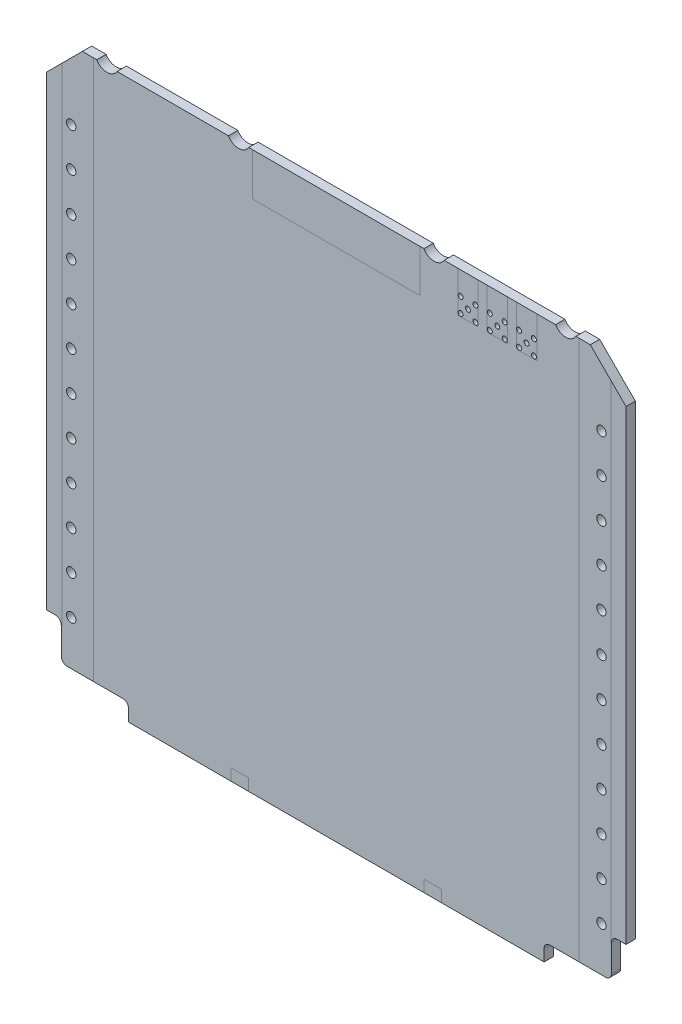
SolidWorks part; units mm, degrees
material "FR4_stuffedProtoboard"
ref_plane "Front Plane" through (0, 0, 0) normal (0, 0, 1) x (1, 0, 0)
ref_plane "Top Plane" through (0, 0, 0) normal (0, 1, 0) x (1, 0, 0)
ref_plane "Right Plane" through (0, 0, 0) normal (1, 0, 0) x (0, 0, -1)
ref_plane "Plane4" through (0, 0, -0.0125) normal (0, 0, -1) x (-1, 0, 0)
sketch "Sketch1" plane through (0, 0, -0.0125) normal (0, 0, -1) x (-1, 0, 0)
  line L4 (49.5, -50) -> (49.5, 45.3)
  line L6 (49.5, 45.3) -> (-49.5, 45.3)
  line L12 (-49.5, 45.3) -> (-49.5, -50)
  line L17 (-49.5, -50) -> (49.5, -50)
  line L18 (0, -50) -> (0, 45.3) construction
  dimension "D7" = 95.3
  dimension "D1" = 99
  dimension "D34" = 50
extrude "basicSize" add sketch "Sketch1" against normal blind 1.6
chamfer "Chamfer1" distance 6.1 angle 45 2 edges at (49.5, 45.3, 0.7875) (-49.5, 45.3, 0.7875)
sketch "Sketch4" plane through (0, 0, 1.5875) normal (0, 0, 1) x (1, 0, 0)
  line L1 (37.4679, 45.3) -> (40.9321, 45.3)
  line L7 (-43.4, 45.3) -> (43.4, 45.3) construction
  line L8 (49.5, 39.2) -> (49.5, -50) construction
  arc A0 (40.9321, 45.3) -> (37.4679, 45.3) centre (39.2, 46.3) cw
  point P5 (39.2, 44.3)
  dimension "D1" = 2
  dimension "D3" = 10.3
  dimension "D2" = 1
extrude "backplaneSideScrewCutout" cut sketch "Sketch4" against normal through all both and the other way through all
pattern_linear "LPattern3" count 2 spacing 22.5 along (-1, 0, 0) of "backplaneSideScrewCutout"
mirror "Mirror3" about plane through (0, 0, 0) normal (1, 0, 0) of "LPattern3"
sketch "Sketch6" plane through (0, 0, 1.5875) normal (0, 0, 1) x (1, 0, 0)
  line L0 (-49.5, -50) -> (-49.5, 39.2) construction
  line L1 (-49.5, -40.4) -> (-47, -40.4)
  line L2 (-49.5, -40.4) -> (-49.5, -50)
  line L4 (-47, -40.4) -> (-47, -47)
  line L5 (49.5, -50) -> (-49.5, -50) construction
  line L6 (-35.5, -50) -> (-49.5, -50)
  line L7 (-35.5, -50) -> (-35.5, -47)
  line L8 (-35.5, -47) -> (-47, -47)
  dimension "D1" = 2.5
  dimension "D2" = 3
  dimension "D3" = 9.6
  dimension "D4" = 14
extrude "Cut-Extrude4" cut sketch "Sketch6" against normal through all
fillet "Fillet1" radius 1 3 edges at (-35.5, -47, 0.7875) (-47, -47, 0.7875) (-47, -40.4, 0.7875)
mirror "Mirror1" about plane through (0, 0, 0) normal (1, 0, 0) of "Cut-Extrude4", "Fillet1"
sketch "Sketch5" plane through (0, 0, 1.5875) normal (0, 0, 1) x (1, 0, 0)
  line L0 (21.23, 41.37) -> (23.77, 38.83) construction
  line L1 (21.23, 38.83) -> (21.23, 41.37) construction
  line L2 (21.23, 41.37) -> (23.77, 41.37) construction
  line L4 (49.5, 39.2) -> (49.5, -40.4) construction
  line L5 (-14.9679, 45.3) -> (14.9679, 45.3) construction
  circle A0 centre (22.5, 40.1) radius 0.425
  circle A1 centre (21.23, 41.37) radius 0.425
  circle A3 centre (21.23, 38.83) radius 0.425
  circle A4 centre (23.77, 41.37) radius 0.425
  circle A5 centre (23.77, 38.83) radius 0.425
  dimension "D2" = 0.85
  dimension "D1" = 2.54
  dimension "D3" = 3.93
  dimension "D4" = 28.27
extrude "Cut-Extrude3" cut sketch "Sketch5" against normal through all
pattern_linear "LPattern2" count 3 spacing 5 along (1, 0, 0) of "Cut-Extrude3"
sketch "partFootprints" plane through (0, 0, 1.5875) normal (0, 0, 1) x (1, 0, 0)
  line L1 (18.4321, 45.3) -> (37.4679, 45.3) construction
  line L6 (20.75, 45.3) -> (20.75, 38.35)
  line L7 (20.75, 38.35) -> (24.25, 38.35)
  line L8 (24.25, 38.35) -> (24.25, 45.3)
  line L9 (24.25, 45.3) -> (20.75, 45.3)
  line L10 (25.75, 45.3) -> (25.75, 38.35)
  line L11 (25.75, 38.35) -> (29.25, 38.35)
  line L12 (29.25, 38.35) -> (29.25, 45.3)
  line L13 (29.25, 45.3) -> (25.75, 45.3)
  line L14 (30.75, 45.3) -> (30.75, 38.35)
  line L15 (30.75, 38.35) -> (34.25, 38.35)
  line L16 (34.25, 38.35) -> (34.25, 45.3)
  line L17 (34.25, 45.3) -> (30.75, 45.3)
  line L19 (32.5, 38.35) -> (32.5, 40.1) construction
  line L23 (22.5, 38.35) -> (22.5, 40.1) construction
  circle A2 centre (22.5, 40.1) radius 0.425 construction
  circle A5 centre (32.5, 40.1) radius 0.425 construction
  dimension "D1" = 1.75
  dimension "D8" = 3.5
  dimension "D6" = 3
extrude "MMCXfootprint" cut sketch "partFootprints" against normal blind 0.0001
sketch "Sketch7" plane through (0, 0, 1.5875) normal (0, 0, 1) x (1, 0, 0)
  line L0 (-14.2875, 45.5) -> (-14.2875, 39.912) construction
  line L1 (-14.2875, 45.3) -> (-14.2875, 38.007)
  line L2 (-12.2428, 38.007) -> (-11.8872, 38.007) construction
  line L3 (-14.2875, 38.007) -> (14.2875, 38.007)
  line L4 (14.2875, 45.5) -> (14.2875, 39.912) construction
  line L5 (14.2875, 45.3) -> (14.2875, 38.007)
  line L7 (-14.9679, 45.3) -> (14.9679, 45.3) construction
  line L8 (-14.2875, 45.3) -> (14.2875, 45.3)
extrude "TigerEyeFootprint" cut sketch "Sketch7" against normal blind 0.0001
sketch "thermalContacts_upper" plane through (0, 0, 1.5875) normal (0, 0, 1) x (1, 0, 0)
  line L0 (-49.5, -40.4) -> (-49.5, 39.2) construction
  line L1 (35.5, -50) -> (-35.5, -50) construction
  line L3 (-46.9, 45.3) -> (-46.9, -41.5)
  line L4 (-37.4679, 45.3) -> (-18.4321, 45.3) construction
  line L23 (-46.9, 45.3) -> (-56.3922, 45.3)
  line L24 (-56.3922, 45.3) -> (-56.3922, -41.5)
  line L25 (-56.3922, -41.5) -> (-46.9, -41.5)
  point P2 (-47.2, 47)
  dimension "D1" = 2.6
  dimension "D2" = 8.5
extrude "keepOut_bottom" cut sketch "thermalContacts_upper" against normal blind 0.0001
sketch "Sketch3" plane through (0, 0, 1.5875) normal (0, 0, 1) x (1, 0, 0)
  line L0 (18.4321, 45.3) -> (20.75, 45.3) construction
  line L1 (-47, -46) -> (-47, -41.5) construction
  line L2 (-36.5, -47) -> (-46, -47) construction
  line L5 (-49.5, -40.4) -> (-49.5, 39.2) construction
  line L6 (-46.9, -41.5) -> (-46.9, 41.8) construction
  line L7 (-46.9, -41.5) -> (-47, -41.5)
  line L8 (-47, -46) -> (-47, -41.5) construction
  line L9 (-47, -41.5) -> (-46.9, -41.5) construction
  line L10 (0, -50) -> (0, 45.3) construction
  line L11 (35.5, -50) -> (-35.5, -50) construction
  line L12 (-43.4, 45.3) -> (-40.9321, 45.3) construction
  line L13 (-41.5, 45.3) -> (-46.9, 45.3)
  line L14 (-46, -47) -> (-41.5, -47)
  line L15 (-47, -41.5) -> (-47, -46)
  line L16 (-46.9, 45.3) -> (-46.9, -41.5)
  line L17 (-41.5, -47) -> (-41.5, 45.3)
  arc A3 (-47, -46) -> (-46, -47) centre (-46, -46) ccw construction
  arc A4 (-46, -47) -> (-47, -46) centre (-46, -46) cw
  point P0 (-41.7, 45.3)
  dimension "D1" = 8
extrude "caution_top" cut sketch "Sketch3" against normal blind 0.0001
sketch "hold-downLocations" plane through (0, 0, 1.5875) normal (0, 0, 1) x (1, 0, 0)
  line L1 (-18, -48) -> (-15, -48) construction
  line L3 (15, -48) -> (18, -48)
  line L4 (18, -48) -> (18, -50)
  line L5 (35.5, -50) -> (-35.5, -50) construction
  line L6 (18, -50) -> (15, -50)
  line L7 (15, -50) -> (15, -48)
  line L8 (-15, -48) -> (-15, -50) construction
  line L9 (-15, -50) -> (-18, -50) construction
  line L10 (-18, -50) -> (-18, -48) construction
  line L11 (0, -50) -> (0, -48) construction
  line L12 (-15, -48) -> (15, -48) construction
  point P13 (0, 0)
  point P14 (0, 0)
  point P15 (18, -45.9002)
  dimension "D1" = 3
  dimension "D2" = 2
  dimension "D3" = 3
  dimension "D5" = 30
extrude "hold-downFootprints" cut sketch "hold-downLocations" against normal blind 0.0001
ref_plane "midplane_Z" through (0, 0, 0.7875) normal (0, 0, 1) x (1, 0, 0)
mirror "clearances_top-bottom" about plane through (0, 0, 0.7875) normal (0, 0, 1) of "hold-downFootprints", "caution_top", "keepOut_bottom"
mirror "clearances_side-side" about plane through (0, 0, 0) normal (1, 0, 0) of "clearances_top-bottom"
sketch "recommendedBuildArea" [suppressed] plane through (0, 0, 1.5875) normal (0, 0, 1) x (1, 0, 0)
  line L0 (51.1146, 38.007) -> (51.1146, 56.8216) construction
  line L1 (-35.5, -45.5) -> (-46.8, -45.5) construction
  line L2 (-35.5, -47) -> (-35.5, -45.5) construction
  line L3 (35.5, -47) -> (35.5, -45.5) construction
  line L4 (14.2875, 45.3) -> (-14.2875, 45.3)
  line L5 (-14.2875, 45.3) -> (-14.2875, 38.007)
  line L6 (-14.2875, 38.007) -> (14.2875, 38.007)
  line L7 (-46.8, 41.9) -> (-49.5, 39.2)
  line L8 (-49.5, 39.2) -> (-49.5, -40.4)
  line L9 (-49.5, -40.4) -> (-48, -40.4)
  line L10 (-46.8, -41.5) -> (-46.8, 41.9)
  line L11 (-47, -41.4) -> (-47, -41.5)
  line L12 (-47, -41.4) -> (-47, -41.5)
  line L13 (-47, -41.5) -> (-46.8, -41.5)
  line L14 (35.5, -45.5) -> (46.8, -45.5) construction
  line L15 (54.1146, 35.007) -> (54.1146, 77.997)
  line L16 (54.1146, 77.997) -> (43.8, 42.325)
  line L17 (-46.8, -45.5) -> (-46.8, 41.9) construction
  line L20 (43.8, 42.325) -> (43.8, -42.5)
  line L21 (14.2875, 38.007) -> (14.2875, 45.3)
  line L22 (32.5, -42.5) -> (43.8, -42.5)
  line L23 (-14.2875, 45.3) -> (-14.2875, 38.007)
  line L24 (-14.2875, 38.007) -> (51.1146, 38.007)
  line L25 (32.5, -47) -> (32.5, -42.5)
  line L26 (32.5, -47) -> (32.5, -47)
  line L27 (21, -47) -> (32.5, -47)
  line L28 (21, -45) -> (21, -47)
  line L29 (46.8, -41.5) -> (47, -41.5)
  line L30 (46.8, -41.5) -> (47, -41.5)
  line L31 (46.8, 41.9) -> (46.8, -41.5)
  line L32 (48, -40.4) -> (49.5, -40.4)
  line L33 (49.5, -40.4) -> (49.5, 39.2)
  line L34 (49.5, 39.2) -> (46.8, 41.9)
  line L35 (47, -41.5) -> (47, -41.4)
  line L36 (12, -45) -> (21, -45)
  line L37 (47, -41.5) -> (47, -41.4)
  line L38 (46.8, 41.9) -> (46.8, -45.5) construction
  line L39 (12, -47) -> (12, -45)
  line L40 (-12, -47) -> (12, -47)
  line L41 (-12, -45) -> (-12, -47)
  line L42 (-21, -45) -> (-12, -45)
  line L43 (-21, -47) -> (-21, -45)
  line L44 (-32.5, -47) -> (-21, -47)
  line L45 (-32.5, -47) -> (-32.5, -47)
  line L46 (-32.5, -47) -> (-32.5, -42.5)
  line L47 (-32.5, -42.5) -> (-43.8, -42.5)
  line L48 (-43.8, -42.5) -> (-43.8, 34.7661)
  line L49 (-43.8, 34.7661) -> (-43.8, 34.7661)
  line L50 (-43.8, 34.7661) -> (-39.8793, 42.3)
  line L51 (-17.2875, 42.3) -> (-39.8793, 42.3)
  line L52 (-17.2875, 42.3) -> (-17.2875, 35.007)
  line L53 (-17.2875, 35.007) -> (54.1146, 35.007)
  line L59 (-47, -41.5) -> (-46.8, -41.5)
  line L72 (-15, -48) -> (-15, -50)
  line L73 (-15, -50) -> (15, -50)
  line L74 (15, -50) -> (15, -48)
  line L75 (15, -48) -> (18, -48)
  line L76 (18, -48) -> (18, -50)
  line L77 (18, -50) -> (35.5, -50)
  line L78 (35.5, -50) -> (35.5, -48)
  line L79 (36.5, -47) -> (41.5, -47)
  line L80 (41.5, -47) -> (41.5, 45.3)
  line L81 (41.5, 45.3) -> (40.9321, 45.3)
  line L82 (37.4679, 45.3) -> (34.25, 45.3)
  line L83 (34.25, 45.3) -> (34.25, 38.35)
  line L84 (34.25, 38.35) -> (30.75, 38.35)
  line L85 (30.75, 38.35) -> (30.75, 45.3)
  line L86 (30.75, 45.3) -> (29.25, 45.3)
  line L87 (29.25, 45.3) -> (29.25, 38.35)
  line L88 (29.25, 38.35) -> (25.75, 38.35)
  line L89 (25.75, 38.35) -> (25.75, 45.3)
  line L90 (25.75, 45.3) -> (24.25, 45.3)
  line L91 (24.25, 45.3) -> (24.25, 38.35)
  line L92 (24.25, 38.35) -> (20.75, 38.35)
  line L93 (20.75, 38.35) -> (20.75, 45.3)
  line L94 (20.75, 45.3) -> (18.4321, 45.3)
  line L95 (14.9679, 45.3) -> (14.2875, 45.3)
  line L96 (14.2875, 45.3) -> (14.2875, 38.007)
  line L97 (14.2875, 38.007) -> (-14.2875, 38.007)
  line L98 (-14.2875, 38.007) -> (-14.2875, 45.3)
  line L99 (-14.2875, 45.3) -> (-14.9679, 45.3)
  line L100 (-18.4321, 45.3) -> (-37.4679, 45.3)
  line L101 (-40.9321, 45.3) -> (-41.5, 45.3)
  line L102 (41.5, -47) -> (41.5, 45.3)
  line L103 (-41.5, -47) -> (-36.5, -47)
  line L104 (-35.5, -48) -> (-35.5, -50)
  line L105 (-35.5, -50) -> (-18, -50)
  line L106 (-18, -50) -> (-18, -48)
  line L107 (-18, -48) -> (-15, -48)
  line L108 (-15, -48) -> (-15, -50) construction
  line L109 (-15, -50) -> (15, -50) construction
  line L110 (15, -50) -> (15, -48) construction
  line L111 (15, -48) -> (18, -48) construction
  line L112 (18, -48) -> (18, -50) construction
  line L113 (18, -50) -> (35.5, -50) construction
  line L114 (35.5, -50) -> (35.5, -47) construction
  line L115 (35.5, -47) -> (41.5, -47) construction
  line L133 (51.1146, 38.007) -> (-14.2875, 38.007)
  line L134 (-14.2875, 38.007) -> (-14.2875, 45.3)
  line L136 (-14.2875, 45.3) -> (-41.7, 45.3) construction
  line L139 (-41.5, -47) -> (-35.5, -47) construction
  line L140 (-35.5, -47) -> (-35.5, -50) construction
  line L141 (-35.5, -50) -> (-18, -50) construction
  line L142 (-18, -50) -> (-18, -48) construction
  line L143 (-18, -48) -> (-15, -48) construction
  line L144 (-46.8, 35.5) -> (-41.7, 45.3) construction
  line L160 (-41.5, 45.3) -> (-41.5, -47)
  line L161 (-41.5, 45.3) -> (-41.5, -47)
  line L162 (-46.8, 41.9) -> (-46.8, 35.5) construction
  line L163 (51.1146, 56.8216) -> (46.8, 41.9) construction
  arc A1 (-47, -41.4) -> (-48, -40.4) centre (-48, -41.4) ccw
  arc A3 (48, -40.4) -> (47, -41.4) centre (48, -41.4) ccw
  arc A10 (36.5, -47) -> (35.5, -48) centre (36.5, -48) ccw
  arc A11 (37.4679, 45.3) -> (40.9321, 45.3) centre (39.2, 46.3) ccw
  arc A12 (14.9679, 45.3) -> (18.4321, 45.3) centre (16.7, 46.3) ccw
  arc A13 (-18.4321, 45.3) -> (-14.9679, 45.3) centre (-16.7, 46.3) ccw
  arc A14 (-40.9321, 45.3) -> (-37.4679, 45.3) centre (-39.2, 46.3) ccw
  arc A15 (-35.5, -48) -> (-36.5, -47) centre (-36.5, -48) ccw
  dimension "D5" = 1.5
  dimension "D1" = 0
  dimension "D2" = 0
  dimension "D3" = 0
  dimension "D4" = 0
  dimension "D6" = 3
ref_point "rail midpoint"
sketch "locatorSketch" plane through (0, 0, 1.5875) normal (0, 0, 1) x (1, 0, 0)
  line L0 (-12.2428, 39.531) -> (12.2428, 38.007) construction
  line L1 (12.2428, 39.531) -> (-12.2428, 38.007) construction
  line L4 (-12.2428, 38.261) -> (-12.2428, 38.007)
  line L5 (-11.8872, 38.261) -> (-12.2428, 38.261)
  line L6 (-11.8872, 38.007) -> (-11.8872, 38.261)
  line L7 (-12.2428, 38.007) -> (-11.8872, 38.007)
  line L8 (-12.2428, 38.261) -> (-12.2428, 38.007)
  line L9 (-11.8872, 38.261) -> (-12.2428, 38.261)
  line L10 (-11.8872, 38.007) -> (-11.8872, 38.261)
  line L11 (-12.2428, 38.007) -> (-11.8872, 38.007)
  line L12 (-12.2428, 39.531) -> (-12.2428, 39.277)
  line L13 (-11.8872, 39.531) -> (-12.2428, 39.531)
  line L14 (-11.8872, 39.277) -> (-11.8872, 39.531)
  line L15 (-12.2428, 39.277) -> (-11.8872, 39.277)
  line L16 (-12.2428, 39.531) -> (-12.2428, 39.277)
  line L17 (-11.8872, 39.531) -> (-12.2428, 39.531)
  line L18 (-11.8872, 39.277) -> (-11.8872, 39.531)
  line L19 (-12.2428, 39.277) -> (-11.8872, 39.277)
  line L20 (11.8872, 39.531) -> (11.8872, 39.277)
  line L21 (12.2428, 39.531) -> (11.8872, 39.531)
  line L22 (12.2428, 39.277) -> (12.2428, 39.531)
  line L23 (11.8872, 39.277) -> (12.2428, 39.277)
  line L24 (11.8872, 39.531) -> (11.8872, 39.277)
  line L25 (12.2428, 39.531) -> (11.8872, 39.531)
  line L26 (12.2428, 39.277) -> (12.2428, 39.531)
  line L27 (11.8872, 39.277) -> (12.2428, 39.277)
  line L28 (11.8872, 38.261) -> (11.8872, 38.007)
  line L29 (12.2428, 38.261) -> (11.8872, 38.261)
  line L30 (12.2428, 38.007) -> (12.2428, 38.261)
  line L31 (11.8872, 38.007) -> (12.2428, 38.007)
  line L32 (11.8872, 38.261) -> (11.8872, 38.007)
  line L33 (12.2428, 38.261) -> (11.8872, 38.261)
  line L34 (12.2428, 38.007) -> (12.2428, 38.261)
  line L35 (11.8872, 38.007) -> (12.2428, 38.007)
  dimension "D1" = 0
  dimension "D2" = 0
  dimension "D3" = 0
  dimension "D4" = 0
sketch "Sketch8" plane through (0, 0, 1.5875) normal (0, 0, 1) x (1, 0, 0)
  line L0 (-49.5, -40.4) -> (-48, -40.4) construction
  line L2 (-49.5, -40.4) -> (-49.5, 39.2) construction
  line L3 (-41.5, 45.3) -> (-43.4, 45.3) construction
  circle A0 centre (-45.3, 33.5) radius 0.8
  circle A1 centre (-45.3, 26.8727) radius 0.8
  circle A2 centre (-45.3, 20.2455) radius 0.8
  circle A3 centre (-45.3, 13.6182) radius 0.8
  circle A4 centre (-45.3, 6.9909) radius 0.8
  circle A5 centre (-45.3, 0.3636) radius 0.8
  circle A6 centre (-45.3, -6.2636) radius 0.8
  circle A7 centre (-45.3, -12.8909) radius 0.8
  circle A8 centre (-45.3, -19.5182) radius 0.8
  circle A9 centre (-45.3, -26.1455) radius 0.8
  circle A10 centre (-45.3, -32.7727) radius 0.8
  circle A11 centre (-45.3, -39.4) radius 0.8
  dimension "D1" = 1.6
  dimension "D3" = 1
  dimension "D5" = 4.2
  dimension "D6" = 11.8
  dimension "D2" = 12
extrude "Cut-Extrude5" cut sketch "Sketch8" against normal blind 10
mirror "Mirror4" about plane through (0, 0, 0) normal (1, 0, 0) of "Cut-Extrude5"
sketch "Sketch9" plane through (0, 0, 1.5875) normal (0, 0, 1) x (1, 0, 0)
  circle A0 centre (-45.3, 33.5) radius 1.35
  point P5 (0, 0)
  dimension "D1" = 2.7
